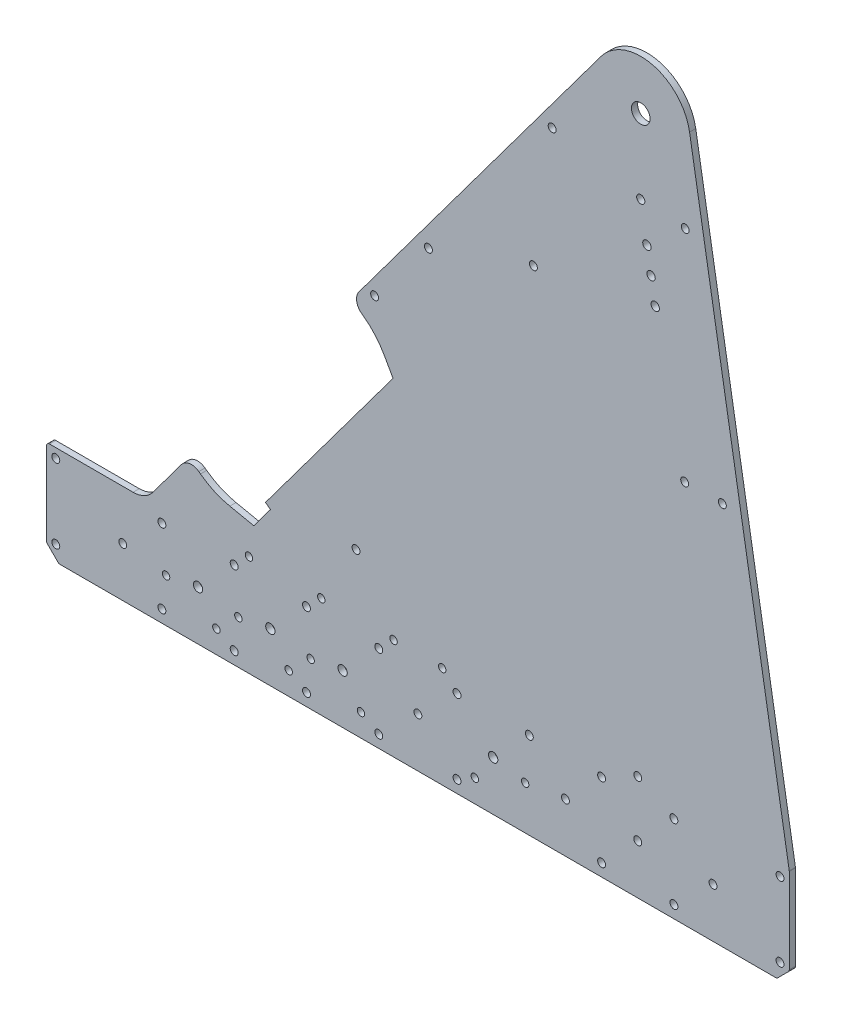
SolidWorks part; units mm, degrees
ref_plane "Front Plane" through (0, 0, 0) normal (0, 0, 1) x (1, 0, 0)
ref_plane "Top Plane" through (0, 0, 0) normal (0, 1, 0) x (1, 0, 0)
ref_plane "Right Plane" through (0, 0, 0) normal (1, 0, 0) x (0, 0, -1)
sketch "Sketch1" plane through (0, 0, 0) normal (0, 0, 1) x (1, 0, 0)
  line L1 (0, 0) -> (381, 0)
  line L2 (0, 0) -> (0, 50.8)
  line L4 (381, 0) -> (381, 50.8)
  line L5 (381, 50.8) -> (329.8448, 353.4827)
  line L6 (0, 50.8) -> (44.4242, 50.8)
  line L7 (54.6089, 55.913) -> (73.025, 80.6347)
  line L9 (112.3289, 80.2488) -> (177.7421, 168.0591)
  line L11 (156.4817, 192.6662) -> (284.4306, 364.4239)
  line L12 (112.3289, 80.2488) -> (114.875, 78.3521)
  line L13 (114.875, 78.3521) -> (106.3397, 66.8943)
  line L14 (156.4817, 192.6662) -> (169.2125, 183.1825)
  line L15 (169.2125, 183.1825) -> (177.7421, 168.0591)
  line L16 (73.025, 80.6347) -> (85.7559, 71.151)
  line L17 (85.7559, 71.151) -> (106.3397, 66.8943)
  line L18 (169.2125, 183.1825) -> (85.7559, 71.151) construction
  arc A0 (284.4306, 364.4239) -> (329.8448, 353.4827) centre (304.8, 349.25) cw
  arc A1 (44.4242, 50.8) -> (54.6089, 55.913) centre (44.4242, 63.5) ccw
  point P11 (50.8, 50.8)
  dimension "D4" = 349.25
  dimension "D7" = 12.7
  dimension "D5" = 25.4
  dimension "D1" = 50.8
  dimension "D2" = 381
  dimension "D3" = 76.2
  dimension "D6" = 50.8
  dimension "D8" = 123.825
  dimension "D9" = 139.7
  dimension "D10" = 15.875
  dimension "D11" = 31.75
  dimension "D12" = 73.025
  dimension "D13" = 3.175
  dimension "D14" = 14.2875
  dimension "D15" = 115
extrude "Boss-Extrude1" add sketch "Sketch1" along normal blind 3.175
sketch "Sketch2" plane through (0, 0, 3.175) normal (0, 0, 1) x (1, 0, 0)
  line L1 (190.5, 50.8) -> (190.5, 0) construction
  line L3 (0, 0) -> (381, 0) construction
  line L5 (0, 6.35) -> (0, 0)
  line L6 (0, 50.8) -> (0, 0) construction
  line L7 (0, 0) -> (6.35, 0)
  line L8 (6.35, 0) -> (0, 6.35)
  line L9 (381, 0) -> (374.65, 0)
  line L10 (374.65, 0) -> (381, 6.35)
  line L11 (381, 6.35) -> (381, 0)
  circle A19 centre (4.7625, 46.0375) radius 2.032
  circle A20 centre (4.7625, 7.9375) radius 2.032
  circle A21 centre (376.2375, 7.9375) radius 2.032
  circle A22 centre (376.2375, 46.0375) radius 2.032
  dimension "D21" = 6.35
  dimension "D27" = 4.064
  dimension "D4" = 46.0375
  dimension "D22" = 6.35
  dimension "D25" = 4.7625
  dimension "D28" = 7.9375
extrude "Cut-Extrude1" cut sketch "Sketch2" against normal up to next
sketch "Sketch5" plane through (0, 0, 3.175) normal (0, 0, 1) x (1, 0, 0)
  line L0 (151.892, 25.4) -> (229.108, 25.4) construction
  line L1 (229.108, 25.4) -> (341.884, 25.4) construction
  circle A0 centre (39.116, 25.4) radius 2.032
  circle A1 centre (59.182, 6.35) radius 2.032
  circle A2 centre (59.182, 44.45) radius 2.032
  circle A3 centre (96.266, 44.45) radius 2.032
  circle A4 centre (133.35, 44.45) radius 2.032
  circle A5 centre (170.434, 44.45) radius 2.032
  circle A6 centre (210.566, 44.45) radius 2.032
  circle A7 centre (210.566, 6.35) radius 2.032
  circle A8 centre (170.434, 6.35) radius 2.032
  circle A9 centre (247.65, 44.45) radius 2.032
  circle A10 centre (266.192, 25.4) radius 2.032
  circle A11 centre (39.116, 25.4) radius 2.286 construction
  circle A12 centre (59.182, 44.45) radius 1.905 construction
  circle A13 centre (59.182, 6.35) radius 1.905 construction
  circle A14 centre (96.266, 44.45) radius 1.905 construction
  circle A15 centre (133.35, 44.45) radius 1.905 construction
  circle A16 centre (170.434, 44.45) radius 1.905 construction
  circle A17 centre (170.434, 6.35) radius 2.159 construction
  circle A18 centre (210.566, 6.35) radius 2.159 construction
  circle A19 centre (210.566, 44.45) radius 1.905 construction
  circle A20 centre (247.65, 44.45) radius 1.905 construction
  circle A21 centre (266.192, 25.4) radius 1.905 construction
  circle A22 centre (77.724, 25.4) radius 2.3813
  circle A23 centre (114.808, 25.4) radius 2.3813
  circle A24 centre (151.892, 25.4) radius 2.3813
  circle A25 centre (229.108, 25.4) radius 2.3813
  circle A26 centre (190.5, 25.4) radius 2.032
  circle A28 centre (303.276, 25.4) radius 2.032
  circle A29 centre (341.884, 25.4) radius 2.032
  circle A30 centre (77.724, 25.4) radius 7.366 construction
  circle A31 centre (114.808, 25.4) radius 7.366 construction
  circle A32 centre (151.892, 25.4) radius 7.366 construction
  circle A33 centre (229.108, 25.4) radius 7.366 construction
  dimension "D1" = 4.064
  dimension "D2" = 4.7625
  dimension "D3" = 37.084
  dimension "D4" = 38.608
  dimension "D5" = 38.608
extrude "Cut-Extrude4" cut sketch "Sketch5" against normal through all
sketch "Sketch6" plane through (0, 0, 3.175) normal (0, 0, 1) x (1, 0, 0)
  line L0 (6.35, 0) -> (374.65, 0) construction
  line L1 (266.192, 25.4) -> (303.276, 25.4) construction
  line L2 (284.734, 6.35) -> (284.734, 44.45) construction
  line L3 (151.892, 25.4) -> (114.808, 25.4) construction
  line L4 (114.808, 25.4) -> (77.724, 25.4) construction
  circle A0 centre (284.734, 44.45) radius 2.032
  circle A1 centre (284.734, 6.35) radius 2.032
  circle A2 centre (321.818, 6.35) radius 2.032
  circle A3 centre (321.818, 44.45) radius 2.032
  circle A4 centre (96.266, 6.35) radius 2.032
  circle A5 centre (133.35, 6.35) radius 2.032
  circle A6 centre (303.276, 53.975) radius 2.032
  arc A7 (304.329, 52.3875) -> (302.223, 52.3875) centre (303.276, 53.975) ccw construction
  point P8 (284.734, 25.4)
  point P9 (284.734, 25.4)
  point P28 (96.266, 25.4)
  point P30 (133.35, 25.4)
  dimension "D1" = 4.064
  dimension "D2" = 6.35
  dimension "D3" = 37.084
extrude "Cut-Extrude5" cut sketch "Sketch6" against normal through all
sketch "Sketch3" plane through (0, 0, 3.175) normal (0, 0, 1) x (1, 0, 0)
  line L0 (73.025, 80.6347) -> (54.6089, 55.913) construction
  line L1 (381, 6.35) -> (381, 50.8) construction
  line L2 (6.35, 0) -> (374.65, 0) construction
  line L3 (304.8, 349.25) -> (304.8, 311.15) construction
  line L4 (307.9745, 292.3664) -> (304.8, 311.15) construction
  line L5 (307.9745, 292.3664) -> (310.0909, 279.8439) construction
  line L6 (310.0909, 279.8439) -> (312.2073, 267.3215) construction
  line L7 (381, 50.8) -> (329.8448, 353.4827) construction
  line L8 (73.025, 80.6347) -> (54.6089, 55.913) construction
  line L9 (0, 50.8) -> (0, 6.35) construction
  circle A0 centre (304.8, 349.25) radius 4.7625
  circle A1 centre (168.275, 200.025) radius 2.032
  circle A2 centre (158.75, 82.55) radius 2.032
  circle A3 centre (304.8, 311.15) radius 2.0955
  circle A5 centre (307.9745, 292.3664) radius 2.159
  circle A6 centre (310.0909, 279.8439) radius 2.159
  circle A7 centre (312.2073, 267.3215) radius 2.159
  circle A8 centre (327.6094, 309.5518) radius 2.032
  circle A9 centre (346.6566, 196.85) radius 2.032
  circle A10 centre (195.8987, 234.95) radius 2.032
  circle A11 centre (249.7483, 254.0902) radius 2.032
  circle A12 centre (259.3534, 320.1311) radius 2.032
  circle A13 centre (327.3365, 196.85) radius 2.032
  point P39 (0, 0)
  dimension "D1" = 9.525
  dimension "D3" = 4.064
  dimension "D6" = 4.064
  dimension "D11" = 4.318
  dimension "D10" = 4.191
  dimension "D13" = 4.064
  dimension "D20" = 4.064
  dimension "D4" = 222.25
  dimension "D5" = 82.55
  dimension "D7" = 19.05
  dimension "D8" = 12.7
  dimension "D9" = 38.1
  dimension "D12" = 12.7
  dimension "D14" = 9.525
  dimension "D15" = 9.525
  dimension "D16" = 114.3
  dimension "D17" = 196.85
  dimension "D18" = 6.35
  dimension "D19" = 234.95
  dimension "D21" = 57.15
  dimension "D22" = 38.1
  dimension "D23" = 53.975
  dimension "D24" = 6.35
  dimension "D25" = 200.025
  dimension "D26" = 168.275
  dimension "D27" = 28.575
extrude "Cut-Extrude2" cut sketch "Sketch3" against normal through all
fillet "Fillet1" radius 1.5875 6 edges at (374.65, 0, 1.5875) (381, 6.35, 1.5875) (381, 50.8, 1.5875) (6.35, 0, 1.5875) (0, 6.35, 1.5875) (0, 50.8, 1.5875)
sketch "Sketch4" plane through (0, 0, 0) normal (0, 0, -1) x (-1, 0, 0)
  circle A0 centre (-61.3181, 22.2981) radius 1.905 construction
  circle A1 centre (-87.1313, 11.606) radius 1.905 construction
  circle A2 centre (-98.4021, 22.2981) radius 1.905 construction
  circle A3 centre (-124.2153, 11.606) radius 1.905 construction
  circle A4 centre (-135.4861, 22.2981) radius 1.905 construction
  circle A5 centre (-161.2993, 11.606) radius 1.905 construction
  circle A6 centre (-245.5139, 22.2981) radius 1.905 construction
  circle A7 centre (-219.7007, 11.606) radius 1.905 construction
  circle A8 centre (-202.982, 51.9684) radius 1.905 construction
  circle A9 centre (-178.018, 51.9684) radius 1.905 construction
  circle A10 centre (-140.934, 51.9684) radius 1.905 construction
  circle A11 centre (-103.85, 51.9684) radius 1.905 construction
  circle A12 centre (-61.3181, 22.2981) radius 1.905
  circle A13 centre (-87.1313, 11.606) radius 1.905
  circle A14 centre (-98.4021, 22.2981) radius 1.905
  circle A15 centre (-124.2153, 11.606) radius 1.905
  circle A16 centre (-135.4861, 22.2981) radius 1.905
  circle A17 centre (-161.2993, 11.606) radius 1.905
  circle A18 centre (-245.5139, 22.2981) radius 1.905
  circle A19 centre (-219.7007, 11.606) radius 1.905
  circle A20 centre (-202.982, 51.9684) radius 1.905
  circle A21 centre (-178.018, 51.9684) radius 1.905
  circle A22 centre (-140.934, 51.9684) radius 1.905
  circle A23 centre (-103.85, 51.9684) radius 1.905
extrude "Cut-Extrude3" cut sketch "Sketch4" against normal up to next
fillet "Fillet2" radius 38.1 2 edges at (85.7559, 71.151, 1.5875) (169.2125, 183.1825, 1.5875)
fillet "Fillet3" radius 6.35 2 edges at (73.025, 80.6347, 1.5875) (156.4817, 192.6662, 1.5875)
